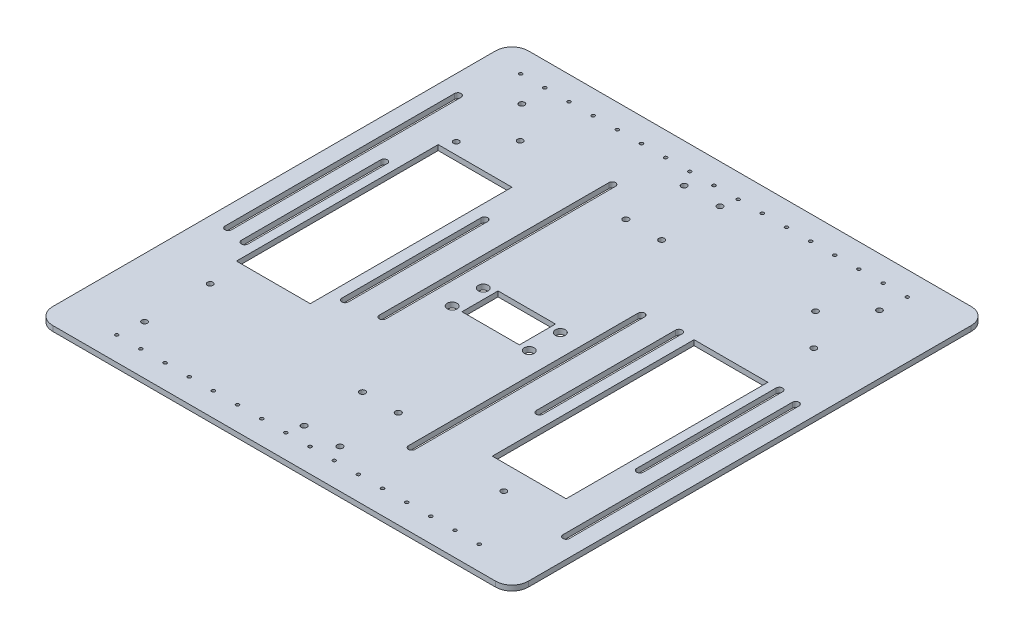
SolidWorks part; units mm, degrees
ref_plane "Front Plane" through (0, 0, 0) normal (0, 0, 1) x (1, 0, 0)
ref_plane "Top Plane" through (0, 0, 0) normal (0, 1, 0) x (1, 0, 0)
ref_plane "Right Plane" through (0, 0, 0) normal (1, 0, 0) x (0, 0, -1)
sketch "Sketch1" plane through (0, 0, 0) normal (0, 1, 0) x (1, 0, 0)
  line L0 (-145, 130.5) -> (145, 130.5) construction
  line L1 (145, -145) -> (-145, -145)
  line L2 (145, -145) -> (145, 145)
  line L3 (145, 145) -> (-145, 145)
  line L4 (-145, -145) -> (-145, 145)
  line L5 (145, -145) -> (-145, 145) construction
  line L6 (145, 145) -> (-145, -145) construction
  line L7 (-145, 116) -> (145, 116) construction
  line L8 (-145, 101.5) -> (145, 101.5) construction
  line L9 (-145, 87) -> (145, 87) construction
  line L10 (-145, 72.5) -> (145, 72.5) construction
  line L11 (-145, 58) -> (145, 58) construction
  line L12 (-145, 43.5) -> (145, 43.5) construction
  line L13 (-145, 29) -> (145, 29) construction
  line L14 (-145, 14.5) -> (145, 14.5) construction
  line L15 (-145, 0) -> (145, 0) construction
  line L16 (-145, -14.5) -> (145, -14.5) construction
  line L17 (-145, -29) -> (145, -29) construction
  line L18 (-145, -43.5) -> (145, -43.5) construction
  line L19 (-145, -58) -> (145, -58) construction
  line L20 (-145, -72.5) -> (145, -72.5) construction
  line L21 (-145, -87) -> (145, -87) construction
  line L22 (-145, -101.5) -> (145, -101.5) construction
  line L23 (-145, -116) -> (145, -116) construction
  line L24 (-145, -130.5) -> (145, -130.5) construction
  line L25 (-145, -145) -> (145, -145) construction
  point P0 (0, 0)
  dimension "D1" = 290
  dimension "D2" = 290
  dimension "D3" = 14.5
  dimension "D5" = 14.5
  dimension "D4" = 20
extrude "Base Plate" add sketch "Sketch1" along normal blind 3.175
hole_wizard "Caster Holes" positions "Sketch2" profile "Sketch3" hole size "Ø2.0" standard "ANSI Metric" end condition through all
sketch "Sketch2" plane through (0, 3.175, 0) normal (0, 1, 0) x (1, 0, 0)
  line L5 (0, -145) -> (0, 145) construction
  line L6 (145, 145) -> (-145, 145) construction
  line L8 (-145, 0) -> (145, 0) construction
  line L9 (-145, 0) -> (145, 0) construction
  line L10 (-145, 130.5) -> (145, 130.5) construction
  point P200 (-7.366, 130.5)
  point P217 (-22.098, 130.5)
  point P218 (-36.83, 130.5)
  point P219 (-51.562, 130.5)
  point P220 (-66.294, 130.5)
  point P221 (-81.026, 130.5)
  point P222 (-95.758, 130.5)
  point P223 (-110.49, 130.5)
  point P224 (110.49, 130.5)
  point P225 (95.758, 130.5)
  point P226 (81.026, 130.5)
  point P227 (66.294, 130.5)
  point P228 (51.562, 130.5)
  point P229 (36.83, 130.5)
  point P230 (22.098, 130.5)
  point P231 (7.366, 130.5)
  point P232 (7.366, -130.5)
  point P233 (22.098, -130.5)
  point P234 (36.83, -130.5)
  point P235 (51.562, -130.5)
  point P236 (66.294, -130.5)
  point P237 (81.026, -130.5)
  point P238 (95.758, -130.5)
  point P239 (110.49, -130.5)
  point P240 (-110.49, -130.5)
  point P241 (-95.758, -130.5)
  point P242 (-81.026, -130.5)
  point P243 (-66.294, -130.5)
  point P244 (-51.562, -130.5)
  point P245 (-36.83, -130.5)
  point P246 (-22.098, -130.5)
  point P247 (-7.366, -130.5)
  point P250 (-125.222, 130.5)
  dimension "D1" = 7.366
  dimension "D3" = 14.732
  dimension "D2" = 9
sketch "Sketch3" plane through (-125.222, 3.175, -130.5) normal (1, 0, 0) x (0, 0, 1)
  line L0 (0, 0) -> (0, 3.175)
  line L1 (0, 3.175) -> (1, 3.175)
  line L2 (1, 3.175) -> (1, 0)
  line L5 (1, 0) -> (0, 0)
  line L11 (0, -6.35) -> (0, 107.95) construction
  dimension "Thru Hole Dia." = 2
  dimension "Thru Hole Depth" = 3.175
fillet "Fillet1" radius 10 4 edges at (145, 1.5875, 145) (-145, 1.5875, 145) (145, 1.5875, -145) (-145, 1.5875, -145)
sketch "Sketch4" plane through (0, 0, 0) normal (0, -1, 0) x (1, 0, 0)
  line L0 (145, 0) -> (-145, 0) construction
  line L1 (-145, -135) -> (-145, 135) construction
  line L2 (0, -145) -> (0, 145) construction
  line L3 (-135, 145) -> (135, 145) construction
  point P6 (0, 0)
  point P12 (0, 0)
sketch "Sketch5" plane through (0, 3.175, 0) normal (0, 1, 0) x (1, 0, 0)
  line L0 (0, 145) -> (0, -145) construction
  line L1 (145, 0) -> (-145, 0) construction
  line L2 (0, 145) -> (0, -145) construction
  line L4 (-17.5, -13) -> (17.5, -13)
  line L5 (-17.5, -13) -> (-17.5, 9)
  line L6 (-17.5, 9) -> (17.5, 9)
  line L7 (17.5, -13) -> (17.5, 9)
  line L8 (-17.5, -13) -> (17.5, 9) construction
  line L9 (-17.5, 9) -> (17.5, -13) construction
  circle A0 centre (-23.5, 6) radius 3
  circle A2 centre (-23.5, -13) radius 3
  circle A3 centre (23.5, 6) radius 3
  circle A4 centre (23.5, -13) radius 3
  point P13 (0, -2)
  dimension "D1" = 6
  dimension "D2" = 23.5
  dimension "D3" = 6
  dimension "D4" = 19
  dimension "D5" = 6
  dimension "D6" = 6
extrude "Reflect Holes" cut sketch "Sketch5" against normal up to surface (3.175 mm away) up to face at (-7.366, 0, -129.5)
sketch "Sketch6" plane through (0, 3.175, 0) normal (0, 1, 0) x (1, 0, 0)
  line L0 (-133, 145) -> (-133, -145) construction
  line L1 (135, 145) -> (-135, 145) construction
  line L2 (-135, -145) -> (135, -145) construction
  line L3 (-145, 135) -> (-145, -135) construction
  line L4 (-133, 100) -> (-133, -40) construction
  line L5 (-131, 100) -> (-131, -40)
  line L6 (-135, 100) -> (-135, -40)
  line L7 (-38.9, 100) -> (-38.9, -40) construction
  line L8 (-36.9, 100) -> (-36.9, -40)
  line L9 (-40.9, 100) -> (-40.9, -40)
  line L10 (-120.5, 42.5) -> (-120.5, -42.5) construction
  line L11 (-118.5, 42.5) -> (-118.5, -42.5)
  line L12 (-122.5, 42.5) -> (-122.5, -42.5)
  line L13 (-59.3, 42.5) -> (-59.3, -42.5) construction
  line L14 (-57.3, 42.5) -> (-57.3, -42.5)
  line L15 (-61.3, 42.5) -> (-61.3, -42.5)
  line L16 (145, 0) -> (-145, 0) construction
  line L17 (0, -145) -> (0, 145) construction
  line L18 (38.9, 100) -> (38.9, -40) construction
  line L19 (36.9, 100) -> (36.9, -40) construction
  line L20 (40.9, 100) -> (40.9, -40) construction
  line L21 (59.3, 42.5) -> (59.3, -42.5) construction
  line L22 (57.3, 42.5) -> (57.3, -42.5)
  line L23 (61.3, 42.5) -> (61.3, -42.5)
  line L24 (120.5, 42.5) -> (120.5, -42.5) construction
  line L25 (118.5, 42.5) -> (118.5, -42.5)
  line L26 (122.5, 42.5) -> (122.5, -42.5)
  line L27 (133, 100) -> (133, -40) construction
  line L28 (131, 100) -> (131, -40) construction
  line L29 (135, 100) -> (135, -40) construction
  line L30 (133, -100) -> (133, 40) construction
  line L31 (131, -100) -> (131, 40)
  line L32 (135, -100) -> (135, 40)
  line L33 (38.9, -100) -> (38.9, 40) construction
  line L34 (36.9, -100) -> (36.9, 40)
  line L35 (40.9, -100) -> (40.9, 40)
  arc A0 (-131, 100) -> (-135, 100) centre (-133, 100) ccw
  arc A1 (-135, -40) -> (-131, -40) centre (-133, -40) ccw
  arc A4 (-36.9, 100) -> (-40.9, 100) centre (-38.9, 100) ccw
  arc A5 (-40.9, -40) -> (-36.9, -40) centre (-38.9, -40) ccw
  arc A6 (-118.5, 42.5) -> (-122.5, 42.5) centre (-120.5, 42.5) ccw
  arc A7 (-122.5, -42.5) -> (-118.5, -42.5) centre (-120.5, -42.5) ccw
  arc A8 (-57.3, 42.5) -> (-61.3, 42.5) centre (-59.3, 42.5) ccw
  arc A9 (-61.3, -42.5) -> (-57.3, -42.5) centre (-59.3, -42.5) ccw
  arc A10 (36.9, 100) -> (40.9, 100) centre (38.9, 100) cw construction
  arc A11 (40.9, -40) -> (36.9, -40) centre (38.9, -40) cw construction
  arc A12 (57.3, 42.5) -> (61.3, 42.5) centre (59.3, 42.5) cw
  arc A13 (61.3, -42.5) -> (57.3, -42.5) centre (59.3, -42.5) cw
  arc A14 (118.5, 42.5) -> (122.5, 42.5) centre (120.5, 42.5) cw
  arc A15 (122.5, -42.5) -> (118.5, -42.5) centre (120.5, -42.5) cw
  arc A16 (131, 100) -> (135, 100) centre (133, 100) cw construction
  arc A17 (135, -40) -> (131, -40) centre (133, -40) cw construction
  arc A18 (131, -100) -> (135, -100) centre (133, -100) ccw
  arc A19 (135, 40) -> (131, 40) centre (133, 40) ccw
  arc A20 (36.9, -100) -> (40.9, -100) centre (38.9, -100) ccw
  arc A21 (40.9, 40) -> (36.9, 40) centre (38.9, 40) ccw
  point P10 (-133, 30)
  point P15 (-38.9, 30)
  point P27 (-120.5, 0)
  point P34 (-59.3, 0)
  point P44 (0, 0)
  point P46 (0, 0)
  point P48 (38.9, 30)
  point P55 (59.3, 0)
  point P62 (120.5, 0)
  point P69 (133, 30)
  point P76 (133, -30)
  point P83 (38.9, -30)
  dimension "D3" = 2
  dimension "D6" = 2
  dimension "D1" = 12
  dimension "D2" = 140
  dimension "D4" = 94.1
  dimension "D5" = 12.5
  dimension "D7" = 85
  dimension "D8" = 61.2
  dimension "D9" = 45
extrude "bearing slots" cut sketch "Sketch6" against normal up to surface (3.175 mm away) up to face at (23.5, 0, -3)
sketch "Sketch7" plane through (0, 3.175, 0) normal (0, 1, 0) x (1, 0, 0)
  line L0 (-145, 135) -> (-145, -135) construction
  line L9 (-113, 43) -> (-68, 43)
  line L10 (-113, 43) -> (-113, -55)
  line L11 (-113, -55) -> (-68, -55)
  line L12 (-68, 43) -> (-68, -55)
  point P9 (-68, -6)
  dimension "D2" = 98
  dimension "D1" = 45
  dimension "D3" = 32
  dimension "D4" = 6
extrude "wheel slots" cut sketch "Sketch7" against normal up to surface (3.175 mm away) up to face at (-133, 0, -30)
mirror "Mirror2" about plane through (0, 0, 0) normal (1, 0, 0) of "wheel slots"
sketch "Sketch9" plane through (0, 3.175, 0) normal (0, 1, 0) x (1, 0, 0)
  line L0 (-109, -145) -> (-109, 145) construction
  line L1 (135, 145) -> (-135, 145) construction
  line L2 (-145, 135) -> (-145, -135) construction
  line L3 (-135, -145) -> (135, -145) construction
  line L4 (90, -145) -> (90, 145) construction
  line L5 (145, -135) -> (145, 135) construction
  point P0 (-109, -75)
  point P1 (-109, -115)
  point P2 (90, -95)
  point P8 (-109, 0)
  point P21 (90, 0)
  dimension "D1" = 36
  dimension "D2" = 70
  dimension "D3" = 30
  dimension "D4" = 55
  dimension "D5" = 50
hole_wizard "standoff holes" positions "Sketch10" profile "Sketch11" hole size "M3" standard "ANSI Metric" end condition through all
sketch "Sketch10" plane through (0, 3.175, 0) normal (0, 1, 0) x (1, 0, 0)
  line L0 (145, 0) -> (-145, 0) construction
  line L1 (-145, 135) -> (-145, -135) construction
  line L2 (0, -145) -> (0, 145) construction
  line L3 (135, 145) -> (-135, 145) construction
  line L4 (145, -145) -> (-145, 145) construction
  point P0 (-109, -75)
  point P3 (-109, -115)
  point P6 (90, -95)
  point P56 (0, 0)
  point P105 (0, 0)
  point P230 (0, 0)
  point P231 (90, 95)
  point P232 (-109, 115)
  point P233 (-109, 75)
  point P235 (-90, 95)
  point P236 (109, 75)
  point P237 (109, 115)
  dimension "D1" = 45
sketch "Sketch11" plane through (-109, 3.175, 75) normal (1, 0, 0) x (0, 0, 1)
  line L0 (0, 0) -> (0, 3.175)
  line L1 (0, 3.175) -> (1.7, 3.175)
  line L2 (1.7, 3.175) -> (1.7, 0)
  line L5 (1.7, 0) -> (0, 0)
  line L11 (0, -6.35) -> (0, 107.95) construction
  dimension "Thru Hole Dia." = 3.4
  dimension "Thru Hole Depth" = 3.175
sketch "Sketch12" plane through (0, 3.175, 0) normal (0, 1, 0) x (1, 0, 0)
  line L10 (-68, 43) -> (-68, -55) construction
  line L11 (-113, 43) -> (-68, 43)
  line L12 (-113, 43) -> (-113, 68)
  line L13 (-113, 68) -> (-68, 68)
  line L14 (-68, 43) -> (-68, 68)
  line L15 (68, -55) -> (113, -55)
  line L16 (68, -55) -> (68, -80)
  line L17 (68, -80) -> (113, -80)
  line L18 (113, -55) -> (113, -80)
  line L19 (113, 43) -> (113, -55) construction
  dimension "D1" = 25
  dimension "D2" = 25
extrude "wheel holes" cut sketch "Sketch12" against normal up to surface (3.175 mm away) up to face at (-109, 0, 76.7)
sketch "Sketch13" plane through (0, 3.175, 0) normal (0, 1, 0) x (1, 0, 0)
  line L0 (0, -145) -> (0, 145) construction
  line L7 (135, 145) -> (-135, 145) construction
  line L8 (19.75, -103.53) -> (-8.75, -103.53) construction
  line L9 (-8.75, -82.38) -> (19.75, -82.38) construction
  line L10 (-8.75, -82.38) -> (-8.75, -124.68) construction
  line L11 (-8.75, -124.68) -> (19.75, -124.68) construction
  line L12 (19.75, -82.38) -> (19.75, -124.68) construction
  line L13 (-8.75, -82.38) -> (19.75, -124.68) construction
  line L14 (-8.75, -124.68) -> (19.75, -82.38) construction
  line L15 (5.5, -124.68) -> (5.5, -82.38) construction
  line L16 (-135, -145) -> (135, -145) construction
  line L17 (145, 0) -> (-145, 0) construction
  line L18 (-145, 135) -> (-145, -135) construction
  line L19 (16.42, -121.312) -> (16.42, -145) construction
  line L20 (-16.34, 121.312) -> (-16.34, 145) construction
  line L21 (0, 121.312) -> (5.5, 121.312) construction
  circle A4 centre (16.42, -85.748) radius 1.75
  circle A6 centre (16.42, -121.312) radius 1.75
  circle A7 centre (-5.42, -121.312) radius 1.75
  circle A8 centre (-5.42, -85.748) radius 1.75
  circle A9 centre (5.5, 85.748) radius 1.75
  circle A10 centre (-16.34, 85.748) radius 1.75
  circle A11 centre (-16.34, 121.312) radius 1.75
  circle A12 centre (5.5, 121.312) radius 1.75
  point P6 (5.5, 121.5469)
  point P12 (0, 0)
  point P16 (0, 0)
  point P22 (5.5, -103.53)
  point P24 (5.5, -103.53)
  point P30 (5.5, -103.53)
  point P32 (0, 0)
  point P38 (-16.34, 121.312)
  point P44 (0.04, 0)
  point P45 (9.1859, 88.2031)
  point P46 (0, 0)
  dimension "D1" = 20.32
  dimension "D2" = 3.5
  dimension "D3" = 2
  dimension "D4" = 5.5
  dimension "D5" = 5.5
  dimension "D6" = 28.5
  dimension "D7" = 42.3
  dimension "D8" = 3.368
  dimension "D9" = 3.33
extrude "Cut-Extrude1" cut sketch "Sketch13" against normal up to surface (3.175 mm away) up to face at (90.5, 0, 18.5)
